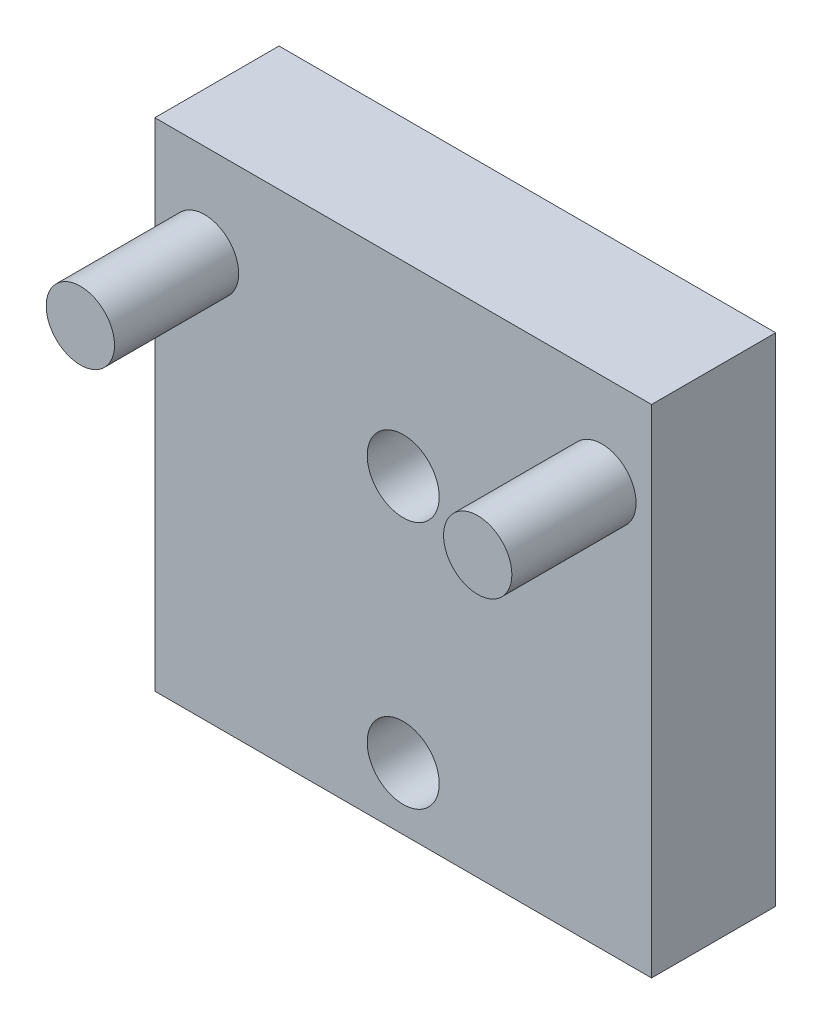
SolidWorks part; units mm, degrees
ref_plane "Front Plane" through (0, 0, 0) normal (0, 0, 1) x (1, 0, 0)
ref_plane "Top Plane" through (0, 0, 0) normal (0, 1, 0) x (1, 0, 0)
ref_plane "Right Plane" through (0, 0, 0) normal (1, 0, 0) x (0, 0, -1)
sketch "Sketch1" plane through (0, 0, 0) normal (0, 0, 1) x (1, 0, 0)
  line L1 (20, -7.5) -> (-20, -7.5)
  line L2 (20, -7.5) -> (20, 7.5)
  line L3 (20, 7.5) -> (-20, 7.5)
  line L4 (-20, -7.5) -> (-20, 7.5)
  line L5 (0, 7.5) -> (0, -7.5) construction
  line L6 (20, 0) -> (-20, 0) construction
  point P0 (0, 0)
  dimension "D1" = 40
  dimension "D2" = 15
extrude "Boss-Extrude1" add sketch "Sketch1" against normal blind 10
sketch "Sketch2" plane through (0, 0, 0) normal (0, 0, 1) x (1, 0, 0)
  line L0 (-16, 0) -> (16, 0) construction
  circle A0 centre (-16, 0) radius 2.75
  circle A1 centre (16, 0) radius 2.75
  point P4 (-13.4517, 1.0297)
  point P8 (0, 0)
  dimension "D2" = 5.5
  dimension "D1" = 32
extrude "Boss-Extrude2" add sketch "Sketch2" along normal blind 10
sketch "Sketch3" plane through (0, 0, 0) normal (0, 0, 1) x (1, 0, 0)
  line L0 (20, -7.5) -> (20, 7.5) construction
  line L1 (-20, -7.5) -> (20, -7.5)
  line L2 (-20, -7.5) -> (-20, -32.5)
  line L3 (-20, -32.5) -> (20, -32.5)
  line L4 (20, -7.5) -> (20, -32.5)
  line L5 (0, -32.5) -> (0, -7.5) construction
  line L6 (-20, -20) -> (20, -20) construction
  line L7 (-20, -7.5) -> (20, -7.5) construction
  point P4 (20, -7.5)
  point P212 (0, -20)
  dimension "D1" = 25
extrude "Boss-Extrude3" add sketch "Sketch3" against normal blind 10
hole_wizard "M5 Clearance Hole1" positions "Sketch4" profile "Sketch5" hole size "M5" standard "ANSI Metric" end condition through all
sketch "Sketch4" plane through (0, 0, 0) normal (0, 0, 1) x (1, 0, 0)
  line L0 (0, 0) -> (0, -7.5) construction
  line L2 (-20, -32.5) -> (20, -32.5) construction
  point P0 (0, -7.5)
  point P2 (0, -27.5)
  dimension "D1" = 20
  dimension "D2" = 5
sketch "Sketch5" plane through (0, -7.5, 0) normal (1, 0, 0) x (0, -1, 0)
  line L0 (0, 0) -> (0, 10)
  line L1 (0, 10) -> (2.9, 10)
  line L2 (2.9, 10) -> (2.9, 0)
  line L5 (2.9, 0) -> (0, 0)
  line L11 (0, -6.35) -> (0, 107.95) construction
  dimension "Thru Hole Dia." = 5.8
  dimension "Thru Hole Depth" = 10
